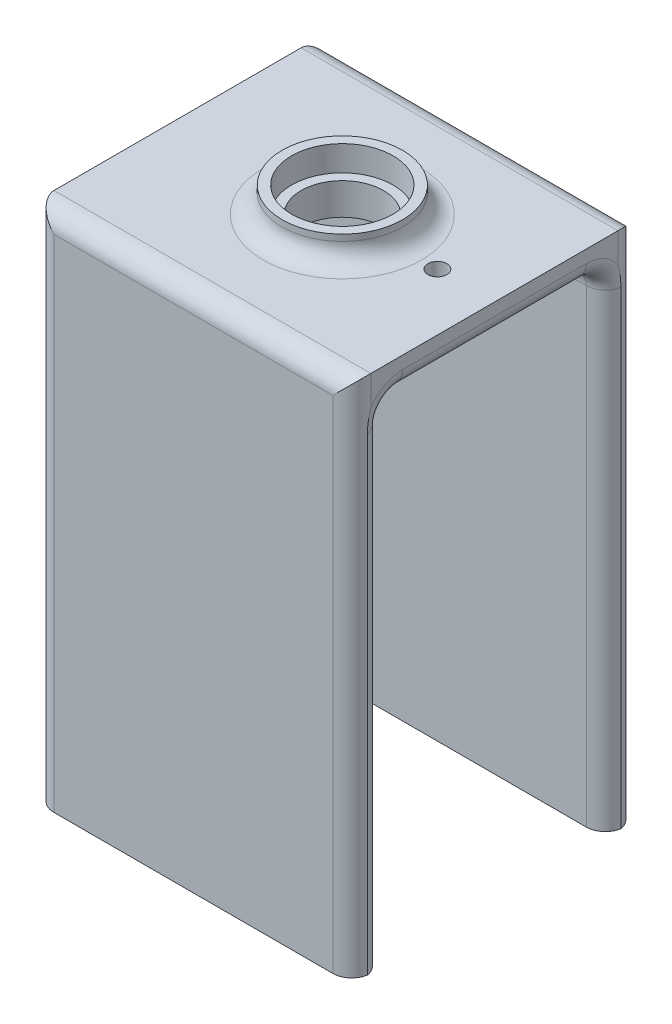
SolidWorks part; units mm, degrees
material "ABS"
ref_plane "Alzado" through (0, 0, 0) normal (0, 0, 1) x (1, 0, 0)
ref_plane "Planta" through (0, 0, 0) normal (0, 1, 0) x (1, 0, 0)
ref_plane "Vista lateral" through (0, 0, 0) normal (1, 0, 0) x (0, 0, -1)
sketch "Croquis1" plane through (0, 0, 0) normal (0, 1, 0) x (1, 0, 0)
  line L1 (-25, -22.5) -> (25, -22.5)
  line L2 (-25, -22.5) -> (-25, 22.5)
  line L3 (-25, 22.5) -> (25, 22.5)
  line L4 (25, -22.5) -> (25, 22.5)
  line L5 (-25, -22.5) -> (25, 22.5) construction
  line L6 (-25, 22.5) -> (25, -22.5) construction
  point P0 (0, 0)
  dimension "D1" = 45
  dimension "D2" = 50
extrude "Saliente-Extruir1" add sketch "Croquis1" along normal blind 82
sketch "Croquis2" plane through (25, 0, 0) normal (1, 0, 0) x (0, 0, -1)
  line L0 (-22.5, 0) -> (22.5, 0) construction
  line L1 (-17.5, 0) -> (17.5, 0)
  line L2 (-17.5, 0) -> (-17.5, 77)
  line L3 (-17.5, 77) -> (17.5, 77)
  line L4 (17.5, 0) -> (17.5, 77)
  line L5 (-22.5, 82) -> (22.5, 82) construction
  line L6 (-22.5, 82) -> (-22.5, 0) construction
  line L7 (22.5, 82) -> (22.5, 0) construction
  dimension "D1" = 5
  dimension "D2" = 5
  dimension "D3" = 5
extrude "Cortar-Extruir1" cut sketch "Croquis2" against normal blind 120
sketch "Croquis3" plane through (0, 82, 0) normal (0, 1, 0) x (1, 0, 0)
  line L0 (-25, 22.5) -> (-25, -22.5) construction
  line L1 (25, -22.5) -> (25, 22.5) construction
  circle A0 centre (1, 0) radius 6.5
  circle A1 centre (16, 0) radius 1.5
  dimension "D1" = 13
  dimension "D2" = 26
  dimension "D3" = 3
  dimension "D4" = 24
  dimension "D5" = 15
extrude "Cortar-Extruir2" cut sketch "Croquis3" against normal blind 20
sketch "Croquis4" plane through (0, 82, 0) normal (0, 1, 0) x (1, 0, 0)
  circle A0 centre (1, 0) radius 9.5
  circle A1 centre (1, 0) radius 8
  dimension "D1" = 19
  dimension "D2" = 16
extrude "Saliente-Extruir2" add sketch "Croquis4" along normal blind 4
sketch "Croquis5" plane through (0, 0, 0) normal (0, -1, 0) x (1, 0, 0)
  line L0 (25, 22.5) -> (25, 17.5) construction
  line L1 (-25, 17.5) -> (-25, 22.5) construction
  line L2 (25, -17.5) -> (25, -22.5) construction
  line L3 (-25, -22.5) -> (-25, -17.5) construction
  circle A0 centre (-13, -20) radius 1.6011
  circle A1 centre (13, -20) radius 1.7209
  circle A2 centre (-13, 20) radius 1.434
  circle A3 centre (13, 20) radius 1.5774
  point P0 (-13, -20)
  point P2 (13, -20)
  point P4 (-13, 20)
  point P6 (13, 20)
  dimension "D2" = 12
  dimension "D1" = 12
  dimension "D3" = 12
  dimension "D4" = 12
hole_wizard "Taladro de margen para M31" positions "Croquis5" profile "Croquis6" hole size "M3" standard "GB"
sketch "Croquis6" plane through (-13, 0, -20) normal (1, 0, 0) x (0, 0, -1)
  line L0 (0, 0) -> (0, 31.0215)
  line L1 (0, 31.0215) -> (1.7, 30)
  line L2 (1.7, 30) -> (1.7, 0)
  line L5 (1.7, 0) -> (0, 0)
  line L10 (0, 31.0215) -> (-1.7, 30) construction
  line L11 (0, -6.35) -> (0, 107.95) construction
  dimension "Diámetro de taladro" = 3.4
  dimension "Profundidad de taladro" = 30
  dimension "Ángulo de perforador" = 118
fillet "Redondeo1" radius 3 14 edges at (25, 77, 0) (0, 77, 17.5) (0, 77, -17.5) (25, 41, -22.5) (25, 38.5, -17.5) (25, 38.5, 17.5) (25, 41, 22.5) (-25, 38.5, 17.5) (-25, 77, 0) (0, 82, 22.5) (0, 82, -22.5) (-25, 41, 22.5) (-25, 41, -22.5) (-25, 38.5, -17.5)
fillet "Redondeo2" radius 3 1 edges at (1, 82, -9.5)
